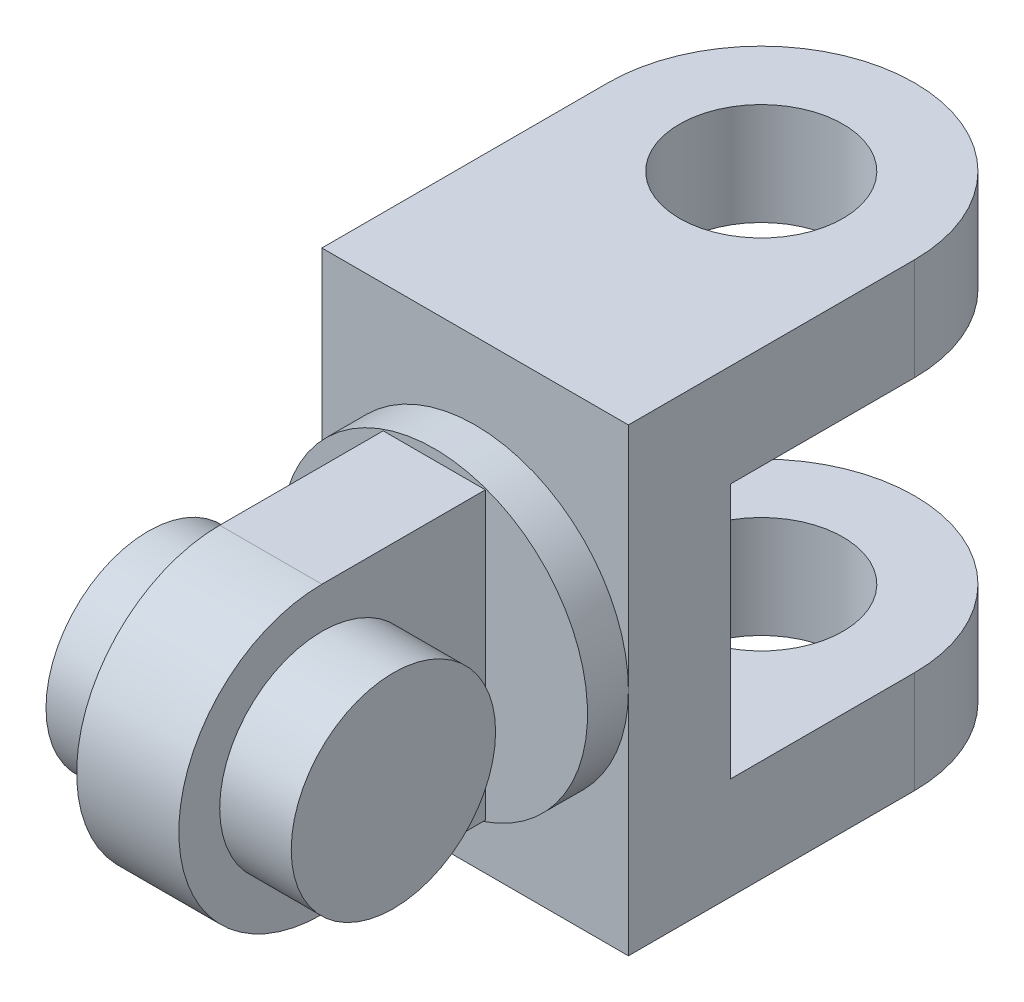
SolidWorks part; units mm, degrees
ref_plane "Front Plane" through (0, 0, 0) normal (0, 0, 1) x (1, 0, 0)
ref_plane "Top Plane" through (0, 0, 0) normal (0, 1, 0) x (1, 0, 0)
ref_plane "Right Plane" through (0, 0, 0) normal (1, 0, 0) x (0, 0, -1)
sketch "Sketch1" plane through (0, 0, 0) normal (1, 0, 0) x (0, 0, -1)
  circle A0 centre (0, 0) radius 10
  dimension "D1" = 20
extrude "Boss-Extrude1" add sketch "Sketch1" along normal mid plane 24
sketch "Sketch2" plane through (0, 0, 0) normal (1, 0, 0) x (0, 0, -1)
  line L0 (0, 14) -> (16, 14)
  line L1 (16, 14) -> (16, -14)
  line L2 (16, -14) -> (0, -14)
  arc A0 (0, 14) -> (0, -14) centre (0, 0) ccw
  dimension "D1" = 28
  dimension "D2" = 16
extrude "Boss-Extrude2" add sketch "Sketch2" along normal mid plane 10
sketch "Sketch3" plane through (0, 0, -16) normal (0, 0, -1) x (-1, 0, 0)
  circle A0 centre (0, 0) radius 15
  dimension "D1" = 30
extrude "Boss-Extrude3" add sketch "Sketch3" along normal blind 4
sketch "Sketch5" plane through (0, 0, -20) normal (0, 0, -1) x (-1, 0, 0)
  line L1 (-15, 22.5) -> (15, 22.5)
  line L2 (-15, 22.5) -> (-15, -22.5)
  line L3 (-15, -22.5) -> (15, -22.5)
  line L4 (15, 22.5) -> (15, -22.5)
  point P4 (-15, 0)
  point P6 (0, -22.5)
  dimension "D1" = 30
  dimension "D2" = 45
extrude "Boss-Extrude4" add sketch "Sketch5" along normal blind 10
sketch "Sketch7" plane through (0, 0, 0) normal (0, 1, 0) x (1, 0, 0)
  line L0 (-15, 30) -> (-15, 48)
  line L1 (-15, 30) -> (15, 30)
  line L2 (15, 48) -> (15, 30)
  arc A0 (-15, 48) -> (15, 48) centre (0, 48) cw
  circle A1 centre (0, 48) radius 8
  dimension "D2" = 16
  dimension "D1" = 18
extrude "Boss-Extrude5" add sketch "Sketch7" along normal up to vertex (22.5 mm away) from offset 12.5 up to point (-15, 22.5, -30)
extrude "Boss-Extrude6" add sketch "Sketch7<2>" against normal blind 10 from offset 12.5 offset against normal yes
sketch "Sketch7<2>" plane through (0, 0, 0) normal (0, 1, 0) x (1, 0, 0) same geometry as "Sketch7"
